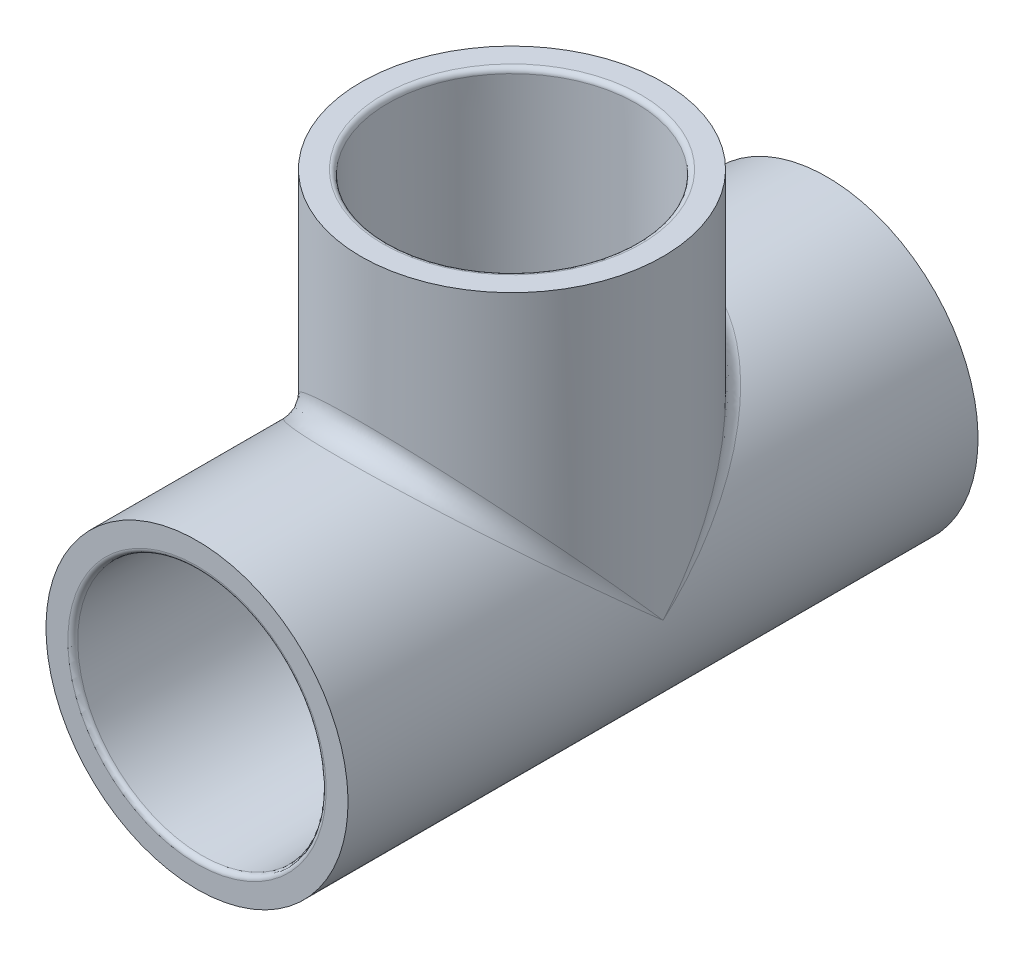
SolidWorks part; units mm, degrees
ref_plane "Front Plane" through (0, 0, 0) normal (0, 0, 1) x (1, 0, 0)
ref_plane "Top Plane" through (0, 0, 0) normal (0, 1, 0) x (1, 0, 0)
ref_plane "Right Plane" through (0, 0, 0) normal (1, 0, 0) x (0, 0, -1)
sketch "Sketch1" plane through (0, 0, 0) normal (1, 0, 0) x (0, 0, -1)
  line L0 (-42.672, 0) -> (42.672, 0) construction
  line L1 (-42.672, 0) -> (-42.672, -20.4597)
  line L2 (-42.672, -20.4597) -> (42.672, -20.4597)
  line L3 (42.672, -20.4597) -> (42.672, 0)
  line L4 (-42.672, -16.8275) -> (-18.034, -16.637)
  line L5 (-18.034, -16.637) -> (-18.034, -15.7607)
  line L6 (-18.034, -15.7607) -> (0, -15.7607)
  line L7 (0, -15.7607) -> (0, 0)
  line L8 (0, -15.7607) -> (0, -20.4597) construction
  point P2 (0, 0)
  dimension "Overall Length" = 85.344
  dimension "Diameter 1" = 33.655
  dimension "Diameter 2" = 33.274
  dimension "Wall 2" = 4.699
  dimension "Wall 1" = 3.6322
  dimension "Socket Depth" = 24.638
sketch "Sketch2" plane through (0, 0, 0) normal (1, 0, 0) x (0, 0, -1)
  line L0 (0, 0) -> (0, 42.672) construction
  line L1 (0, 42.672) -> (20.4597, 42.672)
  line L2 (20.4597, 42.672) -> (20.4597, 0)
  line L3 (-42.672, 0) -> (42.672, 0) construction
  line L4 (20.4597, 0) -> (0, 0)
  line L5 (16.8275, 42.672) -> (16.637, 18.034)
  line L6 (16.637, 18.034) -> (14.5415, 18.034)
  line L7 (14.5415, 18.034) -> (14.5415, 0)
  line L8 (-18.034, -15.7607) -> (0, -15.7607) construction
  dimension "Wall 3" = 3.6322
  dimension "D1" = 33.655
  dimension "D2" = 33.274
  dimension "D3" = 24.638
  dimension "Diameter 3" = 29.083
sketch "Sketch3" plane through (0, 0, 0) normal (1, 0, 0) x (0, 0, -1)
  line L1 (-42.672, 0) -> (42.672, 0)
  line L2 (-42.672, 0) -> (-42.672, -20.4597)
  line L3 (-42.672, -20.4597) -> (42.672, -20.4597)
  line L4 (42.672, 0) -> (42.672, -20.4597)
revolve "Revolve1" add sketch "Sketch3" angle 360 about L1
sketch "Sketch4" plane through (0, 0, 0) normal (1, 0, 0) x (0, 0, -1)
  line L1 (0, 42.672) -> (20.4597, 42.672)
  line L2 (0, 42.672) -> (0, 0)
  line L3 (0, 0) -> (20.4597, 0)
  line L4 (20.4597, 42.672) -> (20.4597, 0)
revolve "Revolve2" add sketch "Sketch4" angle 360 about L2
sketch "Sketch5" plane through (0, 0, 0) normal (1, 0, 0) x (0, 0, -1)
  line L0 (-18.034, -15.7607) -> (0, -15.7607) construction
  line L1 (-18.034, -16.637) -> (-18.034, -15.7607) construction
  line L2 (-42.672, -16.8275) -> (-18.034, -16.637) construction
  line L3 (-18.034, -15.7607) -> (18.034, -15.7607)
  line L4 (-18.034, -16.637) -> (-18.034, -15.7607)
  line L5 (-42.672, -16.8275) -> (-18.034, -16.637)
  line L6 (-42.672, -16.8275) -> (-42.672, 0)
  line L7 (-42.672, 0) -> (42.672, 0)
  line L8 (0, 0) -> (0, -15.7607) construction
  line L9 (18.034, -16.637) -> (18.034, -15.7607)
  line L10 (42.672, -16.8275) -> (18.034, -16.637)
  line L11 (42.672, -16.8275) -> (42.672, 0)
revolve "Cut-Revolve1" cut sketch "Sketch5" angle 360 about L7
sketch "Sketch6" plane through (0, 0, 0) normal (1, 0, 0) x (0, 0, -1)
  line L0 (14.5415, 0) -> (14.5415, 18.034)
  line L1 (14.5415, 18.034) -> (16.637, 18.034)
  line L2 (16.8275, 42.672) -> (16.637, 18.034) construction
  line L3 (16.8275, 42.672) -> (16.637, 18.034)
  line L4 (0, 0) -> (0, 42.672) construction
  line L5 (0, 0) -> (0, 42.672)
  line L6 (0, 42.672) -> (16.8275, 42.672)
  line L7 (0, 0) -> (14.5415, 0)
revolve "Cut-Revolve2" cut sketch "Sketch6" angle 360 about L5
fillet "Fillet1" radius 0.5239 3 edges at (0, -16.637, -18.034) (0, 18.034, -16.637) (0, -16.637, 18.034)
fillet "Fillet2" radius 0.6731 3 edges at (0, -16.8275, -42.672) (0, 42.672, -16.8275) (0, -16.8275, 42.672)
fillet "Fillet3" radius 2.7965 2 edges at (0, 20.4597, 20.4597) (0, 20.4597, -20.4597)
sketch "Sketch7" plane through (0, 0, 0) normal (1, 0, 0) x (0, 0, -1)
  line L0 (-18.034, -15.7607) -> (0, -15.7607) construction
  line L1 (-18.034, -16.637) -> (-18.034, -15.7607) construction
  line L2 (-42.672, -16.8275) -> (-18.034, -16.637) construction
  line L3 (-18.034, -15.7607) -> (18.034, -15.7607)
  line L4 (-18.034, -16.637) -> (-18.034, -15.7607)
  line L5 (-42.672, -16.8275) -> (-18.034, -16.637)
  line L6 (0, 0) -> (0, -15.7607) construction
  line L7 (0, 0) -> (-42.672, 0) construction
  line L8 (-18.034, 15.7607) -> (-14.5415, 15.7607)
  line L9 (-18.034, 16.637) -> (-18.034, 15.7607)
  line L10 (-42.672, 16.8275) -> (-18.034, 16.637)
  line L11 (16.8275, 42.672) -> (16.637, 18.034) construction
  line L12 (16.637, 18.034) -> (14.5415, 18.034) construction
  line L13 (14.5415, 18.034) -> (14.5415, 0) construction
  line L14 (16.8275, 42.672) -> (16.637, 18.034)
  line L15 (16.637, 18.034) -> (14.5415, 18.034)
  line L16 (14.5415, 18.034) -> (14.5415, 15.7607)
  line L17 (-14.5415, 18.034) -> (-14.5415, 15.7607)
  line L18 (-16.637, 18.034) -> (-14.5415, 18.034)
  line L19 (-16.8275, 42.672) -> (-16.637, 18.034)
  line L20 (18.034, -16.637) -> (18.034, -15.7607)
  line L21 (42.672, -16.8275) -> (18.034, -16.637)
  line L22 (18.034, 16.637) -> (18.034, 15.7607)
  line L23 (42.672, 16.8275) -> (18.034, 16.637)
  line L24 (14.5415, 15.7607) -> (18.034, 15.7607)
  point P24 (0, 15.7607)
  point P29 (-42.672, -16.8275)
equation "\"D1@Sketch2\"=\"Diameter 1@Sketch1\""
equation "\"D2@Sketch2\"=\"Diameter 2@Sketch1\""
equation "\"D3@Sketch2\"=\"Socket Depth@Sketch1\""
equation "\"D1@Fillet1\"=0.25*(\"Diameter 2@Sketch1\"-\"Diameter 3@Sketch2\")*0.5"
equation "\"D1@Fillet2\"=.02*\"Diameter 1@Sketch1\""
equation "\"D1@Fillet3\"=.075*(\"Diameter 1@Sketch1\"+\"Wall 1@Sketch1\")"
